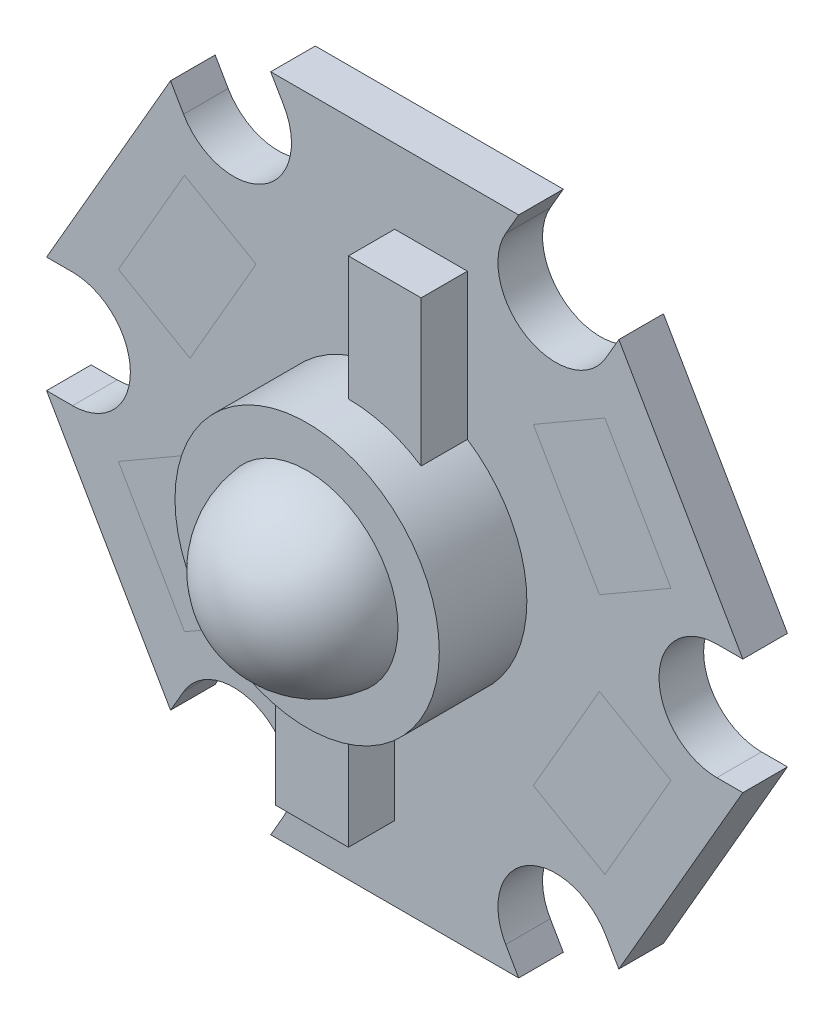
SolidWorks part; units mm, degrees
ref_plane "Front Plane" through (0, 0, 0) normal (0, 0, 1) x (1, 0, 0)
ref_plane "Top Plane" through (0, 0, 0) normal (0, 1, 0) x (1, 0, 0)
ref_plane "Right Plane" through (0, 0, 0) normal (1, 0, 0) x (0, 0, -1)
ref_axis "Axis1" through (0, 0, -0.0675) along (0, 0, 1)
sketch "Sketch1" plane through (0, 0, 0) normal (0, 0, 1) x (1, 0, 0)
  line L1 (5.7735, 10) -> (-5.7735, 10)
  line L2 (-5.7735, 10) -> (-11.547, 0)
  line L3 (-11.547, 0) -> (-5.7735, -10)
  line L4 (-5.7735, -10) -> (5.7735, -10)
  line L5 (5.7735, -10) -> (11.547, 0)
  line L6 (11.547, 0) -> (5.7735, 10)
  circle A0 centre (0, 0) radius 10 construction
  dimension "D1" = 20
extrude "Boss-Extrude1" add sketch "Sketch1" along normal blind 1.35
sketch "Sketch2" plane through (0, 0, 1.35) normal (0, 0, 1) x (1, 0, 0)
  line L0 (-9.75, 0) -> (9.75, 0) construction
  line L1 (-9.75, 1.75) -> (-11.547, 1.75)
  line L2 (-11.547, 1.75) -> (-11.547, -1.75)
  line L3 (-11.547, -1.75) -> (-9.75, -1.75)
  arc A0 (-9.75, -1.75) -> (-9.75, 1.75) centre (-9.75, 0) ccw
  circle A1 centre (9.75, 0) radius 1.75 construction
  dimension "D1" = 16
  dimension "D2" = 3.5
extrude "Cut-Extrude1" cut sketch "Sketch2" against normal through all
pattern_circular "CirPattern1" count 6 over 360 about axis through (0, 0, -0.0675) along (0, 0, 1) of "Cut-Extrude1"
sketch "Sketch4" plane through (0, 0, 0) normal (0, 1, 0) x (1, 0, 0)
  line L0 (-4, -1.35) -> (-4, -4)
  line L1 (-6.3905, -1.35) -> (-3.125, -1.35) construction
  line L2 (-4, -4) -> (-2.75, -4)
  line L3 (-3.7528, 0) -> (3.7528, 0) construction
  line L4 (0, -6.5) -> (0, -1.35)
  line L5 (-3.7528, -1.35) -> (3.7528, -1.35) construction
  line L6 (0, -1.35) -> (-4, -1.35)
  arc A0 (-2.75, -4) -> (0, -6.5) centre (0, -3.7375) ccw
  dimension "D1" = 6.5
  dimension "D2" = 4
  dimension "D3" = 4
  dimension "D4" = 2.75
revolve "Revolve1" add sketch "Sketch4" angle 360 about L4
sketch "Sketch5" plane through (0, 0, 1.35) normal (0, 0, 1) x (1, 0, 0)
  line L1 (0, 7.75) -> (2.2, 7.75)
  line L2 (0, 7.75) -> (0, 3.3407)
  line L3 (0, 3.3407) -> (2.2, 3.3407)
  line L4 (2.2, 7.75) -> (2.2, 3.3407)
  line L5 (0, -7.75) -> (-2.2, -7.75)
  line L6 (0, -7.75) -> (0, -3.3407)
  line L7 (0, -3.3407) -> (-2.2, -3.3407)
  line L8 (-2.2, -7.75) -> (-2.2, -3.3407)
  circle A0 centre (0, 0) radius 4 construction
  circle A1 centre (0, 0) radius 4 construction
  dimension "D1" = 2.2
  dimension "D2" = 15.5
extrude "Boss-Extrude2" add sketch "Sketch5" along normal blind 1.4
sketch "Sketch6" plane through (0, 0, 1.35) normal (0, 0, 1) x (1, 0, 0)
  line L0 (-6.3612, 5.9821) -> (-8.3612, 2.5179)
  line L1 (-8.3612, 2.5179) -> (-6.1962, 1.2679)
  line L2 (-6.1962, 1.2679) -> (-4.1962, 4.7321)
  line L3 (-4.1962, 4.7321) -> (-6.3612, 5.9821)
  line L4 (-6.7839, 8.25) -> (-10.5366, 1.75) construction
  line L5 (-8.6603, 5) -> (-7.3612, 4.25) construction
  line L6 (2, 6) -> (2, 8.5) [skipped]
  line L7 (2, 8.5) -> (-2, 8.5) [skipped]
  line L8 (-2, 6) -> (2, 6) [skipped]
  line L9 (-2, 8.5) -> (-2, 6) [skipped]
  line L10 (6.1962, 1.2679) -> (8.3612, 2.5179)
  line L11 (8.3612, 2.5179) -> (6.3612, 5.9821)
  line L12 (4.1962, 4.7321) -> (6.1962, 1.2679)
  line L13 (6.3612, 5.9821) -> (4.1962, 4.7321)
  line L14 (4.1962, -4.7321) -> (6.3612, -5.9821)
  line L15 (6.3612, -5.9821) -> (8.3612, -2.5179)
  line L16 (6.1962, -1.2679) -> (4.1962, -4.7321)
  line L17 (8.3612, -2.5179) -> (6.1962, -1.2679)
  line L18 (-2, -6) -> (-2, -8.5) [skipped]
  line L19 (-2, -8.5) -> (2, -8.5) [skipped]
  line L20 (2, -6) -> (-2, -6) [skipped]
  line L21 (2, -8.5) -> (2, -6) [skipped]
  line L22 (-6.1962, -1.2679) -> (-8.3612, -2.5179)
  line L23 (-8.3612, -2.5179) -> (-6.3612, -5.9821)
  line L24 (-4.1962, -4.7321) -> (-6.1962, -1.2679)
  line L25 (-6.3612, -5.9821) -> (-4.1962, -4.7321)
  dimension "D1" = 4
  dimension "D2" = 2.5
  dimension "D3" = 1.5
  dimension "D4" = 6
split line "Split Line1"
